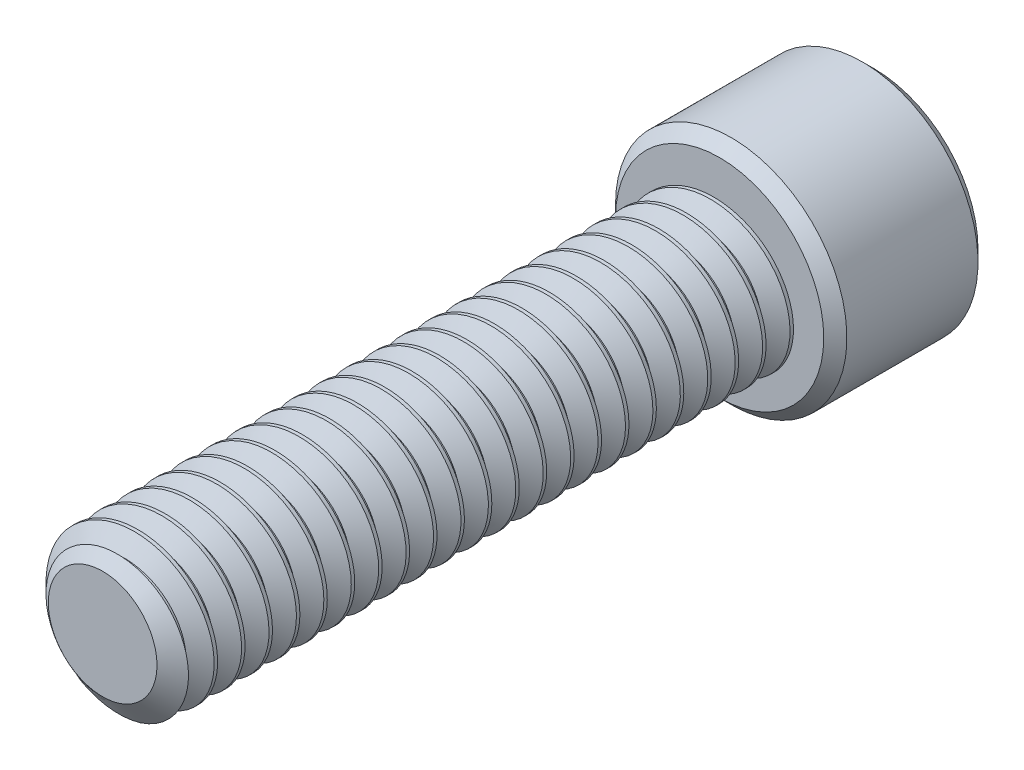
SolidWorks part; units mm, degrees
ref_plane "Front Plane" through (0, 0, 0) normal (0, 0, 1) x (1, 0, 0)
ref_plane "Top Plane" through (0, 0, 0) normal (0, 1, 0) x (1, 0, 0)
ref_plane "Right Plane" through (0, 0, 0) normal (1, 0, 0) x (0, 0, -1)
sketch "Sketch1" plane through (0, 0, 0) normal (0, 0, 1) x (1, 0, 0)
  circle A0 centre (0, 0) radius 3.9688
  dimension "OD" = 7.9375
extrude "Extrude1" add sketch "Sketch1" against normal blind 31.75
sketch "Sketch2" plane through (0, 0, 0) normal (0, 0, 1) x (1, 0, 0)
  circle A0 centre (0, 0) radius 3.9688 construction
  circle A1 centre (0, 0) radius 3.9688
curve "Helix/Spiral1" pitch 1.4111 height 33.1611 turns 23.5 parameters "pitch"=1.4111
sketch "Sketch3" plane through (0, 0, 0) normal (1, 0, 0) x (0, 0, -1)
  line L0 (-1.2347, 3.9688) -> (-0.7056, 3.0522)
  line L1 (-0.7056, 3.0522) -> (-0.5292, 3.0522)
  line L2 (-0.5292, 3.0522) -> (0, 3.9688)
  line L3 (-1.2347, 3.9688) -> (0, 3.9688)
  line L4 (-0.6174, 3.9688) -> (-0.6174, 3.0522) construction
  line L5 (-0.9701, 3.5105) -> (-0.2646, 3.5105) construction
  line L6 (0, 3.9688) -> (0, -3.9688) construction
  dimension "D1" = 0.1764
  dimension "D2" = 0.7056
  dimension "D3" = 60
sweep "Cut-Sweep1" cut profiles "Sketch3" path "Helix/Spiral1"
sketch "Sketch4" plane through (0, 0, 0) normal (1, 0, 0) x (0, 0, -1)
  line L0 (0.8196, 3.9688) -> (0, 2.7982)
  line L1 (0, 2.7982) -> (0, 3.9688)
  line L2 (0.8196, 3.9688) -> (0, 3.9688)
  line L3 (-1.2347, 3.9688) -> (0, 3.9688) construction
  line L4 (0, 0) -> (7.0209, 0) construction
  dimension "D1" = 55
  dimension "D2" = 0.254
revolve "Cut-Revolve1" cut sketch "Sketch4" angle 360 about L4
sketch "Sketch5" plane through (0, 0, 0) normal (1, 0, 0) x (0, 0, -1)
  line L0 (31.75, -2.8318) -> (31.75, 3.0736) construction
  line L1 (31.75, 4.0958) -> (25.5202, 4.0958)
  line L2 (31.75, 4.0958) -> (31.75, 0)
  line L3 (31.75, 0) -> (25.4, 0)
  line L4 (25.4, 3.7656) -> (25.4, 0)
  line L5 (25.5202, 4.0958) -> (25.4, 3.7656)
  line L6 (0, 0) -> (9.9695, 0) construction
  point P3 (25.4, 4.0958)
  point P10 (25.4, 4.0958)
  dimension "D1" = 0.3302
  dimension "Thread min" = 25.4
  dimension "D2" = 0.127
  dimension "D3" = 20
revolve "partially thread" [suppressed] add sketch "Sketch5" angle 360 about L6
sketch "Sketch6" plane through (0, 0, -31.75) normal (0, 0, -1) x (-1, 0, 0)
  circle A0 centre (0, 0) radius 5.9531
  dimension "head dia" = 11.9062
extrude "Extrude2" add sketch "Sketch6" along normal blind 7.9375
sketch "Sketch7" plane through (0, 0, -39.6875) normal (0, 0, -1) x (-1, 0, 0)
  line L1 (0, 3.6662) -> (-3.175, 1.8331)
  line L2 (-3.175, 1.8331) -> (-3.175, -1.8331)
  line L3 (-3.175, -1.8331) -> (0, -3.6662)
  line L4 (0, -3.6662) -> (3.175, -1.8331)
  line L5 (3.175, -1.8331) -> (3.175, 1.8331)
  line L6 (3.175, 1.8331) -> (0, 3.6662)
  circle A0 centre (0, 0) radius 3.175 construction
  dimension "hex dia" = 6.35
extrude "Cut-Extrude1" cut sketch "Sketch7" against normal blind 4.7625
sketch "Sketch8" plane through (0, 0, -39.6875) normal (0, 0, -1) x (-1, 0, 0)
  circle A0 centre (0, 0) radius 3.6662
extrude "Cut-Extrude2" cut sketch "Sketch8" against normal through all draft 45
chamfer "Chamfer1" distance 0.5953 angle 45 2 edges at (-5.9531, 0, -39.6875) (-5.9531, 0, -31.75)
sketch "Sketch9" plane through (0, 0, 0) normal (1, 0, 0) x (0, 0, -1)
  line L0 (0, 3.9688) -> (0, -3.9688) construction
  line L1 (7.7611, 3.9688) -> (7.7611, -3.9688) construction
  dimension "D1" = 7.7611
equation "\"D3@Helix/Spiral1\" = \"screw length@Extrude1\"+\"pitch@Helix/Spiral1\""
equation "\"D1@Sketch3\" = \"pitch@Helix/Spiral1\"*.125"
equation "\"D2@Sketch3\" = \"pitch@Helix/Spiral1\"*.5"
equation "\"D1@Cut-Extrude1\" = \"hex dia@Sketch7\"*.75"
equation "\"D1@Chamfer1\" = \"head dia@Sketch6\"*.05"
equation "\"D1@Sketch9\" = \"pitch@Helix/Spiral1\"*5.5"
